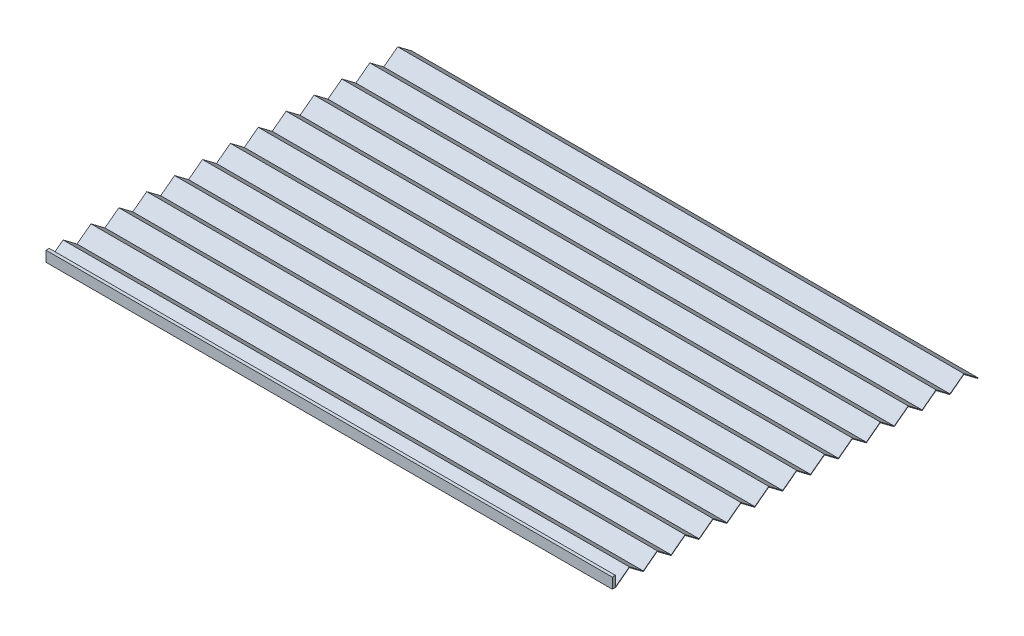
SolidWorks part; units mm, degrees
ref_plane "Front Plane" through (0, 0, 0) normal (0, 0, 1) x (1, 0, 0)
ref_plane "Top Plane" through (0, 0, 0) normal (0, 1, 0) x (1, 0, 0)
ref_plane "Right Plane" through (0, 0, 0) normal (1, 0, 0) x (0, 0, -1)
sketch "Sketch2" plane through (0, 0, 0) normal (0, 0, 1) x (1, 0, 0)
  line L1 (-270, 10) -> (270, 10)
  line L2 (-270, 10) -> (-270, 0)
  line L3 (-270, 0) -> (270, 0)
  line L4 (270, 10) -> (270, 0)
  point P4 (0, 0)
  dimension "D1" = 10
  dimension "D2" = 540
extrude "Boss-Extrude1" add sketch "Sketch2" along normal blind 3
sketch "Sketch3" plane through (270, 0, 0) normal (1, 0, 0) x (0, 0, -1)
  line L0 (0, 10) -> (345.6406, 10) construction
  line L1 (0, 0) -> (345.6406, 0) construction
  line L3 (0, 0) -> (13.2939, 10)
  line L4 (13.2939, 10) -> (26.5877, 0)
  line L5 (26.5877, 0) -> (39.8816, 10)
  line L6 (39.8816, 10) -> (53.1755, 0)
  line L7 (53.1755, 0) -> (66.4693, 10)
  line L8 (66.4693, 10) -> (79.7632, 0)
  line L9 (79.7632, 0) -> (93.0571, 10)
  line L10 (93.0571, 10) -> (106.3509, 0)
  line L11 (106.3509, 0) -> (119.6448, 10)
  line L12 (119.6448, 10) -> (132.9387, 0)
  line L13 (132.9387, 0) -> (146.2325, 10)
  line L14 (146.2325, 10) -> (159.5264, 0)
  line L15 (159.5264, 0) -> (172.8203, 10)
  line L16 (172.8203, 10) -> (186.1141, 0)
  line L17 (186.1141, 0) -> (199.408, 10)
  line L18 (199.408, 10) -> (212.7019, 0)
  line L20 (212.7019, 0) -> (225.9957, 10)
  line L21 (225.9957, 10) -> (239.2896, 0)
  line L22 (239.2896, 0) -> (252.5835, 10)
  line L23 (252.5835, 10) -> (265.8774, 0)
  line L24 (265.8774, 0) -> (279.1712, 10)
  line L25 (279.1712, 10) -> (292.4651, 0)
  line L26 (292.4651, 0) -> (305.759, 10)
  line L27 (305.759, 10) -> (319.0528, 0)
  line L28 (319.0528, 0) -> (332.3467, 10)
  line L29 (332.3467, 10) -> (345.6406, 0)
  line L30 (345.6406, 10) -> (345.6406, 0) construction
  line L32 (345.6406, 10) -> (345.6406, 0) construction
extrude "Extrude-Thin1" add sketch "Sketch3" against normal through all thin thin type mid plane wall 0.5
